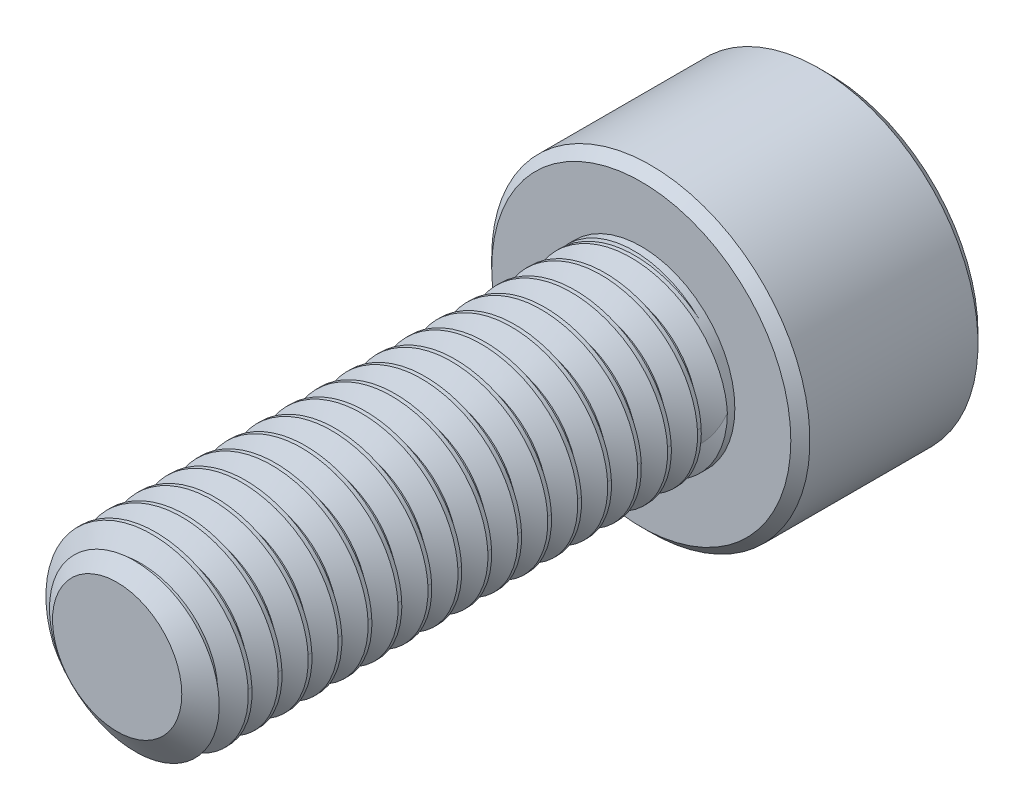
SolidWorks part; units mm, degrees
ref_plane "Front Plane" through (0, 0, 0) normal (0, 0, 1) x (1, 0, 0)
ref_plane "Top Plane" through (0, 0, 0) normal (0, 1, 0) x (1, 0, 0)
ref_plane "Right Plane" through (0, 0, 0) normal (1, 0, 0) x (0, 0, -1)
sketch "Sketch1" plane through (0, 0, 0) normal (0, 0, 1) x (1, 0, 0)
  circle A0 centre (0, 0) radius 2.5
  dimension "OD" = 5
extrude "Extrude1" add sketch "Sketch1" against normal blind 14
sketch "Sketch2" plane through (0, 0, 0) normal (0, 0, 1) x (1, 0, 0)
  circle A0 centre (0, 0) radius 2.5 construction
  circle A1 centre (0, 0) radius 2.5
curve "Helix/Spiral1" pitch 0.8 height 14.8 turns 18.5 parameters "pitch"=0.8
sketch "Sketch3" plane through (0, 0, 0) normal (1, 0, 0) x (0, 0, -1)
  line L0 (-0.7, 2.5) -> (-0.4, 1.9804)
  line L1 (-0.4, 1.9804) -> (-0.3, 1.9804)
  line L2 (-0.3, 1.9804) -> (0, 2.5)
  line L3 (-0.7, 2.5) -> (0, 2.5)
  line L4 (-0.35, 2.5) -> (-0.35, 1.9804) construction
  line L5 (-0.55, 2.2402) -> (-0.15, 2.2402) construction
  line L6 (0, 2.5) -> (0, -2.5) construction
  line L7 (0, -2.5) -> (14, -2.5) construction
  point P11 (3.6, -2.5)
  dimension "D1" = 0.1
  dimension "D2" = 0.4
  dimension "D3" = 60
  dimension "D4" = 3.6
sweep "Cut-Sweep1" cut profiles "Sketch3" path "Helix/Spiral1"
sketch "Sketch4" plane through (0, 0, 0) normal (1, 0, 0) x (0, 0, -1)
  line L0 (0.5417, 2.5) -> (0, 1.7264)
  line L1 (0, 1.7264) -> (0, 2.5)
  line L2 (0.5417, 2.5) -> (0, 2.5)
  line L3 (-0.7, 2.5) -> (0, 2.5) construction
  line L4 (0, 0) -> (7.0209, 0) construction
  dimension "D1" = 55
  dimension "D2" = 0.254
revolve "Cut-Revolve1" cut sketch "Sketch4" angle 360 about L4
sketch "Sketch5" plane through (0, 0, 0) normal (1, 0, 0) x (0, 0, -1)
  line L0 (14, -1.7838) -> (14, 1.991) construction
  line L1 (14, 2.5) -> (0.1203, 2.5)
  line L2 (14, 2.5) -> (14, 0)
  line L3 (14, 0) -> (0.0001, 0)
  line L4 (0.0001, 2.1698) -> (0.0001, 0)
  line L5 (0.1203, 2.5) -> (0.0001, 2.1698)
  line L6 (0, 0) -> (9.9695, 0) construction
  point P3 (0.0001, 2.5)
  point P10 (0.0001, 2.5)
  dimension "D1" = 0.3302
  dimension "Thread min" = 0.0001
  dimension "D3" = 20
revolve "partially thread" [suppressed] add sketch "Sketch5" angle 360 about L6
sketch "Sketch6" plane through (0, 0, -14) normal (0, 0, -1) x (-1, 0, 0)
  circle A0 centre (0, 0) radius 4.25
  dimension "head dia" = 8.5
extrude "Extrude2" add sketch "Sketch6" along normal blind 5
sketch "Sketch7" plane through (0, 0, -19) normal (0, 0, -1) x (-1, 0, 0)
  line L1 (0, 2.3094) -> (-2, 1.1547)
  line L2 (-2, 1.1547) -> (-2, -1.1547)
  line L3 (-2, -1.1547) -> (0, -2.3094)
  line L4 (0, -2.3094) -> (2, -1.1547)
  line L5 (2, -1.1547) -> (2, 1.1547)
  line L6 (2, 1.1547) -> (0, 2.3094)
  circle A0 centre (0, 0) radius 2 construction
  dimension "hex dia" = 4
extrude "Cut-Extrude1" cut sketch "Sketch7" against normal blind 3
sketch "Sketch8" plane through (0, 0, -19) normal (0, 0, -1) x (-1, 0, 0)
  circle A0 centre (0, 0) radius 2.3094
extrude "Cut-Extrude2" cut sketch "Sketch8" against normal through all draft 45
chamfer "Chamfer1" distance 0.255 angle 45 2 edges at (-4.25, 0, -19) (-4.25, 0, -14)
sketch "Sketch9" plane through (0, 0, 0) normal (1, 0, 0) x (0, 0, -1)
  line L0 (0, 2.5) -> (0, -2.5) construction
  line L1 (4.4, 2.5) -> (4.4, -2.5) construction
  dimension "D1" = 4.4
sketch "Sketch10" plane through (0, 0, 0) normal (1, 0, 0) x (0, 0, -1)
  line L0 (14, 2.5) -> (14, 0)
  line L1 (14, 2.5) -> (13.8, 2.5)
  line L2 (13.8, 2.5) -> (12.7645, 0)
  line L3 (14, 0) -> (12.7645, 0)
  line L4 (14, 3.995) -> (14, -3.995) construction
  dimension "D1" = 22.5
  dimension "D2" = 0.2
revolve "Revolve1" add sketch "Sketch10" angle 360 about L3
equation "\"D3@Helix/Spiral1\" = \"screw length@Extrude1\"+\"pitch@Helix/Spiral1\""
equation "\"D1@Sketch3\" = \"pitch@Helix/Spiral1\"*.125"
equation "\"D2@Sketch3\" = \"pitch@Helix/Spiral1\"*.5"
equation "\"D1@Cut-Extrude1\" = \"hex dia@Sketch7\"*.75"
equation "\"D1@Chamfer1\" = \"head dia@Sketch6\"*.03"
equation "\"D1@Sketch9\" = \"pitch@Helix/Spiral1\"*5.5"
equation "\"D2@Sketch10\" = \"pitch@Helix/Spiral1\"*.25"
equation "\"D4@Sketch3\" = \"pitch@Helix/Spiral1\"*4.50"
